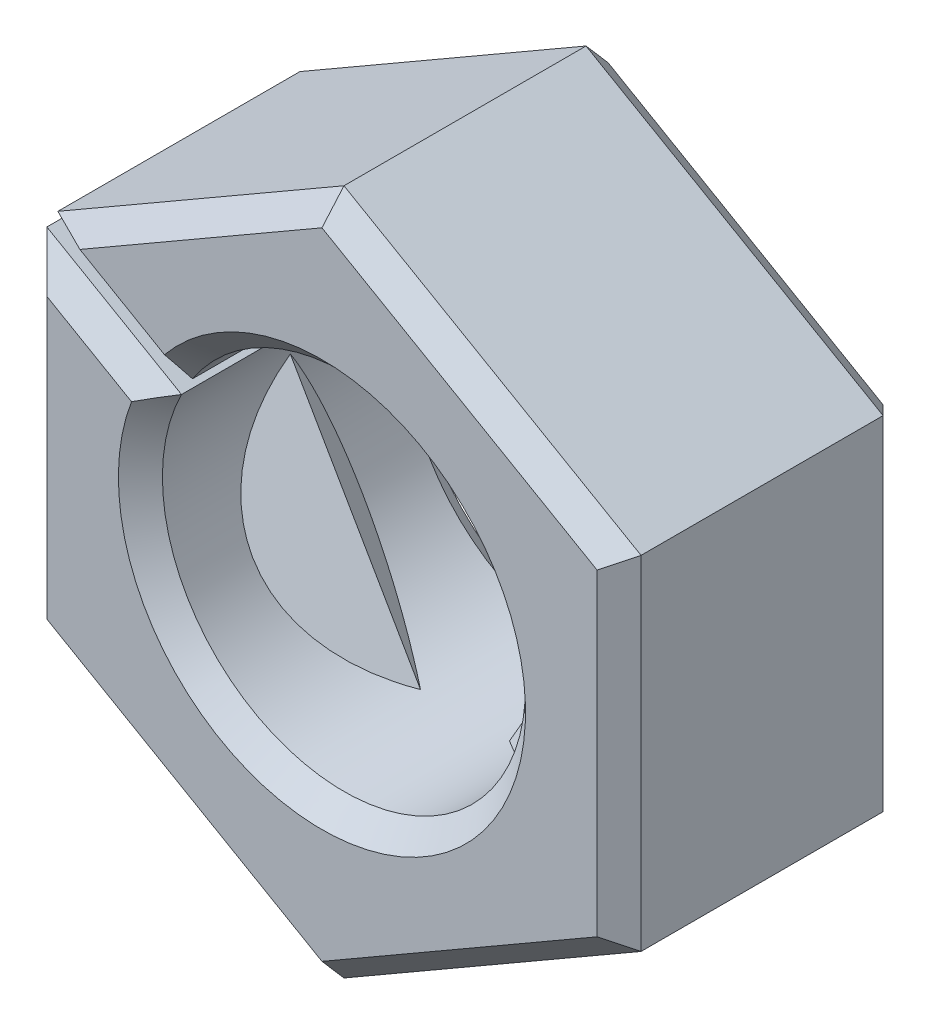
SolidWorks part; units mm, degrees
ref_plane "Front" through (0, 0, 0) normal (0, 0, 1) x (1, 0, 0)
ref_plane "Top" through (0, 0, 0) normal (0, 1, 0) x (1, 0, 0)
ref_plane "Right" through (0, 0, 0) normal (1, 0, 0) x (0, 0, -1)
sketch "Sketch1" plane through (0, 0, 0) normal (0, 0, 1) x (1, 0, 0)
  line L1 (2.7, -1.5588) -> (2.7, 1.5588)
  line L2 (2.7, 1.5588) -> (0, 3.1177)
  line L3 (0, 3.1177) -> (-2.7, 1.5588)
  line L4 (-2.7, 1.5588) -> (-2.7, -1.5588)
  line L5 (-2.7, -1.5588) -> (0, -3.1177)
  line L6 (0, -3.1177) -> (2.7, -1.5588)
  circle A0 centre (0, 0) radius 2.7 construction
  circle A1 centre (0, 0) radius 1.65
  dimension "D1" = 3.3
  dimension "D2" = 5.4
extrude "Boss-Extrude1" add sketch "Sketch1" along normal mid plane 2.6
sketch "Sketch3" plane through (0, 0, 0) normal (1, 0, 0) x (0, 0, -1)
  line L0 (-0.5, 1.65) -> (0.5, 1.65)
  line L1 (1.3, 1.65) -> (-1.3, 1.65) construction
  line L2 (0.5, 1.65) -> (0, 1.15)
  line L3 (0, 1.15) -> (-0.5, 1.65)
  line L4 (0, 0) -> (0, 1.15) construction
  point P6 (-0.5451, 1.65)
  dimension "D1" = 0.5
extrude "Clip" add sketch "Sketch3" along normal up to next and the other way up to next
pattern_circular "Clips x3" count 3 over 360 about axis through (0, 0, 1.3) along (0, 0, 1) of "Clip"
sketch "Sketch4" plane through (0, 0, 0) normal (0, 0, 1) x (1, 0, 0)
  line L0 (-2.7, 1.5588) -> (0, 0)
extrude "Split" cut sketch "Sketch4" against normal through all both and the other way through all thin thin type mid plane wall 0.2
chamfer "Deburs" distance 0.2 angle 45 18 edges at (1.4289, -0.825, -1.3) (2.7, 0, -1.3) (1.35, 2.3383, -1.3) (-1.3, 2.3671, -1.3) (-2.7, -0.0577, -1.3) (-1.35, -2.3383, -1.3) (1.35, -2.3383, -1.3) (1.4289, -0.825, 1.3) (-1.35, -2.3383, 1.3) (-2.7, -0.0577, 1.3) (-1.3, 2.3671, 1.3) (1.35, 2.3383, 1.3) (2.7, 0, 1.3) (1.35, -2.3383, 1.3) (-1.9882, 1.2633, -1.3) (-2.0882, 1.0901, -1.3) (-1.9882, 1.2633, 1.3) (-2.0882, 1.0901, 1.3)
equation "\"D1@Sketch1\"=\"Hardware Clearance Hole Diameter@Box Assy.Assembly\"+.15"
equation "\"D2@Sketch1\"=\"Nut Trap Diameter@Box Assy.Assembly\"-0.3mm"
equation "\"D1@Boss-Extrude1\"=\"Nut Trap Depth@Box Assy.Assembly\""
